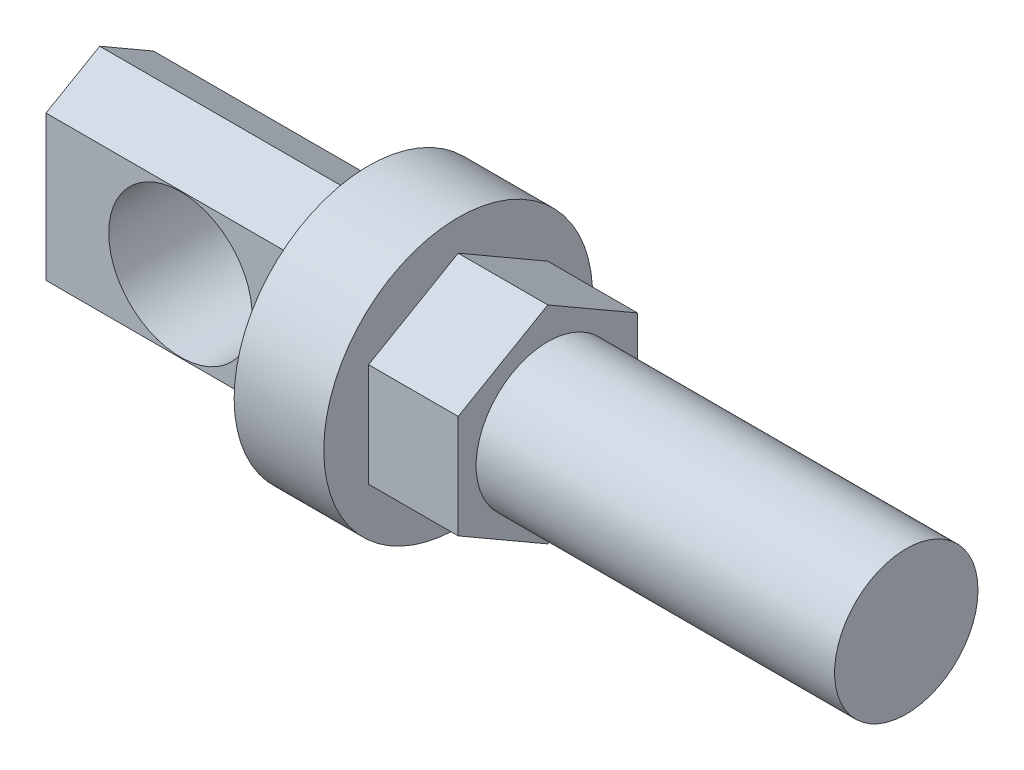
SolidWorks part; units mm, degrees
ref_plane "Спереди" through (0, 0, 0) normal (0, 0, 1) x (1, 0, 0)
ref_plane "Сверху" through (0, 0, 0) normal (0, 1, 0) x (1, 0, 0)
ref_plane "Справа" through (0, 0, 0) normal (1, 0, 0) x (0, 0, -1)
sketch "Эскиз1" plane through (0, 0, 0) normal (1, 0, 0) x (0, 0, -1)
  line L1 (0, 11.547) -> (-10, 5.7735)
  line L2 (-10, 5.7735) -> (-10, -5.7735)
  line L3 (-10, -5.7735) -> (0, -11.547)
  line L4 (0, -11.547) -> (10, -5.7735)
  line L5 (10, -5.7735) -> (10, 5.7735)
  line L6 (10, 5.7735) -> (0, 11.547)
  circle A0 centre (0, 0) radius 10 construction
extrude "Бобышка-Вытянуть1" add sketch "Эскиз1" along normal blind 10
sketch "Эскиз2" plane through (10, 0, 0) normal (1, 0, 0) x (0, 0, -1)
  circle A0 centre (0, 0) radius 8
extrude "Бобышка-Вытянуть2" add sketch "Эскиз2" along normal blind 40
sketch "Эскиз5" plane through (0, 0, 0) normal (-1, 0, 0) x (0, 0, 1)
  circle A0 centre (0, 0) radius 15
extrude "Бобышка-Вытянуть4" add sketch "Эскиз5" along normal blind 10
sketch "Эскиз3" plane through (-10, 0, 0) normal (-1, 0, 0) x (0, 0, 1)
  line L0 (0, 11.547) -> (-6.0017, 8.0819)
  line L2 (-6.0017, 8.0819) -> (-6.0017, -8.0819)
  line L5 (-6.0017, -8.0819) -> (0, -11.547)
  line L6 (0, -11.547) -> (5.9916, -8.0877)
  line L8 (5.9916, -8.0877) -> (5.9916, 8.0877)
  line L10 (5.9916, 8.0877) -> (0, 11.547)
extrude "Бобышка-Вытянуть3" add sketch "Эскиз3" along normal blind 30
sketch "Эскиз4" plane through (0, 0, -6.0017) normal (0, 0, -1) x (-1, 0, 0)
  circle A0 centre (25, 0) radius 8
  point P2 (22.6064, 0)
extrude "Вырез-Вытянуть1" cut sketch "Эскиз4" against normal up to next
